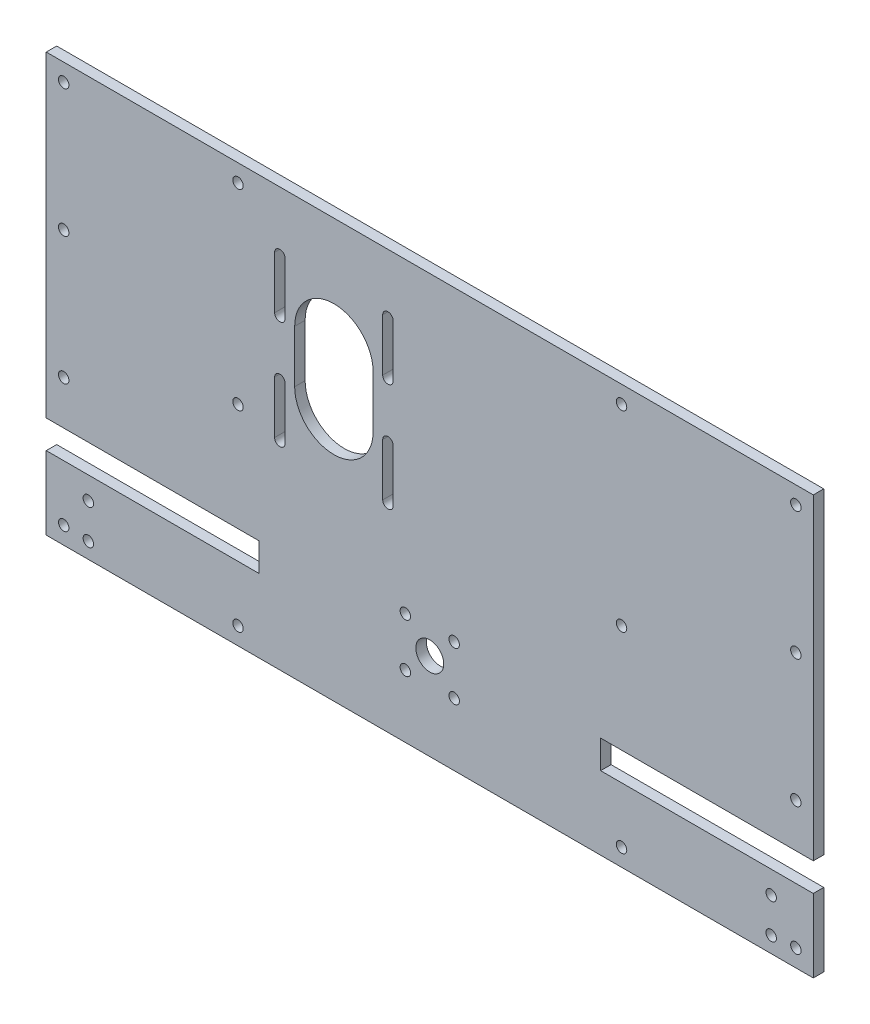
SolidWorks part; units mm, degrees
ref_plane "Plan de face" through (0, 0, 0) normal (0, 0, 1) x (1, 0, 0)
ref_plane "Plan de dessus" through (0, 0, 0) normal (0, 1, 0) x (1, 0, 0)
ref_plane "Plan de droite" through (0, 0, 0) normal (1, 0, 0) x (0, 0, -1)
sketch "Esquisse1" plane through (0, 0, 0) normal (0, 0, 1) x (1, 0, 0)
  line L0 (-27.5, 17.5) -> (-27.5, 32.5) construction
  line L1 (60, -65) -> (-60, -65)
  line L2 (60, -65) -> (60, -34)
  line L3 (60, 65) -> (-60, 65)
  line L4 (-60, -65) -> (-60, -34)
  line L5 (60, -65) -> (-60, 65) construction
  line L6 (60, 65) -> (-60, -65) construction
  line L9 (60, -55) -> (50, -55)
  line L10 (50, -65) -> (50, -55)
  line L13 (-60, -55) -> (-50, -55)
  line L14 (-50, -65) -> (-50, -55)
  line L15 (-38.75, 17.5) -> (-38.75, 32.5)
  line L16 (-16.25, 17.5) -> (-16.25, 32.5)
  line L17 (-43, 33) -> (-43, 48) construction
  line L18 (-44.5, 33) -> (-44.5, 48)
  line L19 (-41.5, 33) -> (-41.5, 48)
  line L20 (-43, 2) -> (-43, 17) construction
  line L21 (-44.5, 2) -> (-44.5, 17)
  line L22 (-41.5, 2) -> (-41.5, 17)
  line L23 (-27.5, 65) -> (-27.5, -65) construction
  line L24 (-27.5, 43.75) -> (-27.5, 6.25) construction
  line L27 (-12, 2) -> (-12, 17) construction
  line L30 (-10.5, 2) -> (-10.5, 17)
  line L31 (-13.5, 2) -> (-13.5, 17)
  line L32 (-12, 33) -> (-12, 48) construction
  line L33 (-10.5, 33) -> (-10.5, 48)
  line L34 (-13.5, 33) -> (-13.5, 48)
  line L35 (-105, -55) -> (-105, 65) construction
  line L36 (-60, -55) -> (-110, -55)
  line L37 (-60, -55) -> (-60, -34)
  line L38 (-60, 65) -> (-110, 65)
  line L39 (-110, -55) -> (-110, 65)
  line L40 (-60, -34) -> (-110, -34)
  line L42 (-60, -25.9) -> (-110, -25.9)
  line L43 (-110, -34) -> (-110, -25.9)
  line L44 (0, 65) -> (0, -65) construction
  line L45 (60, -25.9) -> (110, -25.9)
  line L46 (110, -34) -> (110, -25.9)
  line L47 (60, -34) -> (110, -34)
  line L49 (60, 65) -> (110, 65)
  line L50 (110, -55) -> (110, 65)
  line L51 (60, -55) -> (110, -55)
  line L52 (60, -55) -> (60, -34)
  line L54 (60, -34) -> (49, -34)
  line L55 (-60, -25.9) -> (-49, -25.9)
  line L57 (-60, -34) -> (-49, -34)
  line L58 (-49, -25.9) -> (-49, -34)
  line L59 (49, -25.9) -> (49, -34)
  line L60 (60, -25.9) -> (49, -25.9)
  line L62 (-60, -25.9) -> (-60, 65)
  line L63 (-60, -25.9) -> (-60, 65)
  line L64 (60, -25.9) -> (60, 65)
  line L65 (60, -25.9) -> (60, 65)
  arc A0 (-38.75, 17.5) -> (-16.25, 17.5) centre (-27.5, 17.5) ccw
  arc A1 (-16.25, 32.5) -> (-38.75, 32.5) centre (-27.5, 32.5) ccw
  arc A2 (-44.5, 33) -> (-41.5, 33) centre (-43, 33) ccw
  arc A3 (-41.5, 48) -> (-44.5, 48) centre (-43, 48) ccw
  arc A4 (-44.5, 2) -> (-41.5, 2) centre (-43, 2) ccw
  arc A5 (-41.5, 17) -> (-44.5, 17) centre (-43, 17) ccw
  arc A10 (-10.5, 2) -> (-13.5, 2) centre (-12, 2) cw
  arc A11 (-13.5, 17) -> (-10.5, 17) centre (-12, 17) cw
  arc A12 (-10.5, 33) -> (-13.5, 33) centre (-12, 33) cw
  arc A13 (-13.5, 48) -> (-10.5, 48) centre (-12, 48) cw
  circle A14 centre (-105, -50) radius 1.5
  circle A15 centre (-105, -13.3333) radius 1.5
  circle A16 centre (-105, 23.3333) radius 1.5
  circle A17 centre (-105, 60) radius 1.5
  circle A18 centre (105, -50) radius 1.5
  circle A19 centre (105, -13.3333) radius 1.5
  circle A20 centre (105, 23.3333) radius 1.5
  circle A21 centre (105, 60) radius 1.5
  circle A22 centre (-97.9283, -40.4553) radius 1.5
  circle A26 centre (-97.9283, -50.4553) radius 1.5
  circle A27 centre (97.9283, -50.4553) radius 1.5
  circle A28 centre (97.9283, -40.4553) radius 1.5
  point P0 (0, 0)
  point P14 (-27.5, 25)
  point P21 (-43, 40.5)
  point P28 (-43, 9.5)
  point P37 (-12, 9.5)
  point P44 (-12, 40.5)
  dimension "D13" = 90
  dimension "D17" = 3
  dimension "D22" = 3
  dimension "D23" = 3
  dimension "D1" = 10
  dimension "D2" = 10
  dimension "D3" = 130
  dimension "D4" = 120
  dimension "D5" = 32.5
  dimension "D6" = 15.5
  dimension "D7" = 22.5
  dimension "D8" = 3
  dimension "D9" = 15.5
  dimension "D10" = 15
  dimension "D11" = 3
  dimension "D12" = 31
  dimension "D14" = 8.1
  dimension "D15" = 21
  dimension "D16" = 5
  dimension "D18" = 5
  dimension "D19" = 5
  dimension "D20" = 50
  dimension "D24" = 11
  dimension "D21" = 4
extrude "Boss.-Extru.1" add sketch "Esquisse1" along normal blind 3 contours L14 L1 L10 L9 L2 L3 L4 L37 L13 A5 L22 A4 L21 A3 L19 A2 L18 A1 L16 A0 L15 L31 A11 L30 A10 L34 A13 L33 A12 | L42 L4 L38 L39 A17 A16 A15 | L45 L50 L49 L2 A20 A19 A21 | L2 L51 L50 L47 A18 | L4 L40 L39 L36 A14 region at (1.8169, -0.4375, 0) region at (84.6849, -44.4491, 0) region at (-84.6849, -44.4491, 0) region at (84.9062, 19.5323, 0) region at (-84.9062, 19.5323, 0)
sketch "Esquisse2" plane through (0, 0, 3) normal (0, 0, 1) x (1, 0, 0)
  line L0 (-55, 65) -> (-55, -55) construction
  line L1 (110, 65) -> (-110, 65) construction
  line L2 (110, -55) -> (50, -55) construction
  line L3 (50, -60) -> (-50, -60) construction
  line L4 (50, -65) -> (50, -55) construction
  line L5 (-50, -65) -> (-50, -55) construction
  line L6 (0, 65) -> (0, -65) construction
  line L7 (50, -65) -> (-50, -65) construction
  line L9 (-50, -65) -> (-50, -55) construction
  circle A0 centre (45, -60) radius 1.5
  circle A3 centre (-55, -50) radius 1.5
  circle A4 centre (-55, 5) radius 1.5
  circle A5 centre (-55, 60) radius 1.5
  circle A9 centre (22.5, -60) radius 1.5
  circle A10 centre (0, -60) radius 1.5
  circle A11 centre (-22.5, -60) radius 1.5
  circle A12 centre (-45, -60) radius 1.5
  circle A13 centre (55, -50) radius 1.5
  circle A14 centre (55, 5) radius 1.5
  circle A15 centre (55, 60) radius 1.5
  dimension "D2" = 3
  dimension "D6" = 3
  dimension "D1" = 5
  dimension "D3" = 5
  dimension "D5" = 5
  dimension "D7" = 5
  dimension "D4" = 5
  dimension "D8" = 3
extrude "Enlèv. mat.-Extru.2" cut sketch "Esquisse2" against normal blind 3
sketch "Esquisse3" plane through (0, 0, 3) normal (0, 0, 1) x (1, 0, 0)
  line L3 (50, -65) -> (-50, -65) construction
  line L4 (0, 65) -> (0, -65) construction
  line L5 (110, 65) -> (-110, 65) construction
  line L6 (-7, -23) -> (7, -23) construction
  line L7 (7, -42) -> (-7, -42) construction
  line L8 (12, -37) -> (12, -23) construction
  line L9 (7, -18) -> (-7, -18) construction
  line L10 (-12, -37) -> (-12, -23) construction
  line L11 (12, -42) -> (-12, -18) construction
  line L12 (12, -18) -> (-12, -42) construction
  line L13 (-7, -23) -> (-7, -37) construction
  circle A0 centre (0, -30) radius 4
  arc A2 (-7, -42) -> (-12, -37) centre (-7, -37) cw construction
  arc A3 (7, -42) -> (12, -37) centre (7, -37) ccw construction
  arc A4 (12, -23) -> (7, -18) centre (7, -23) ccw construction
  arc A5 (-7, -18) -> (-12, -23) centre (-7, -23) ccw construction
  circle A6 centre (-7, -23) radius 1.5
  circle A7 centre (7, -23) radius 1.5
  circle A8 centre (7, -37) radius 1.5
  circle A9 centre (-7, -37) radius 1.5
  dimension "D1" = 8
  dimension "D2" = 35
  dimension "D3" = 14
  dimension "D4" = 5
  dimension "D5" = 3
  dimension "D8" = 14
  dimension "D6" = 2
  dimension "D7" = 2
extrude "Enlèv. mat.-Extru.3" cut sketch "Esquisse3" against normal blind 10
sketch "Esquisse4" plane through (0, 0, 3) normal (0, 0, 1) x (1, 0, 0)
  line L0 (-50, -55) -> (50, -55)
  line L1 (50, -55) -> (50, -76.4572)
  line L2 (50, -76.4572) -> (-50, -76.4572)
  line L3 (-50, -76.4572) -> (-50, -55)
extrude "Enlèv. mat.-Extru.4" cut sketch "Esquisse4" against normal blind 10
